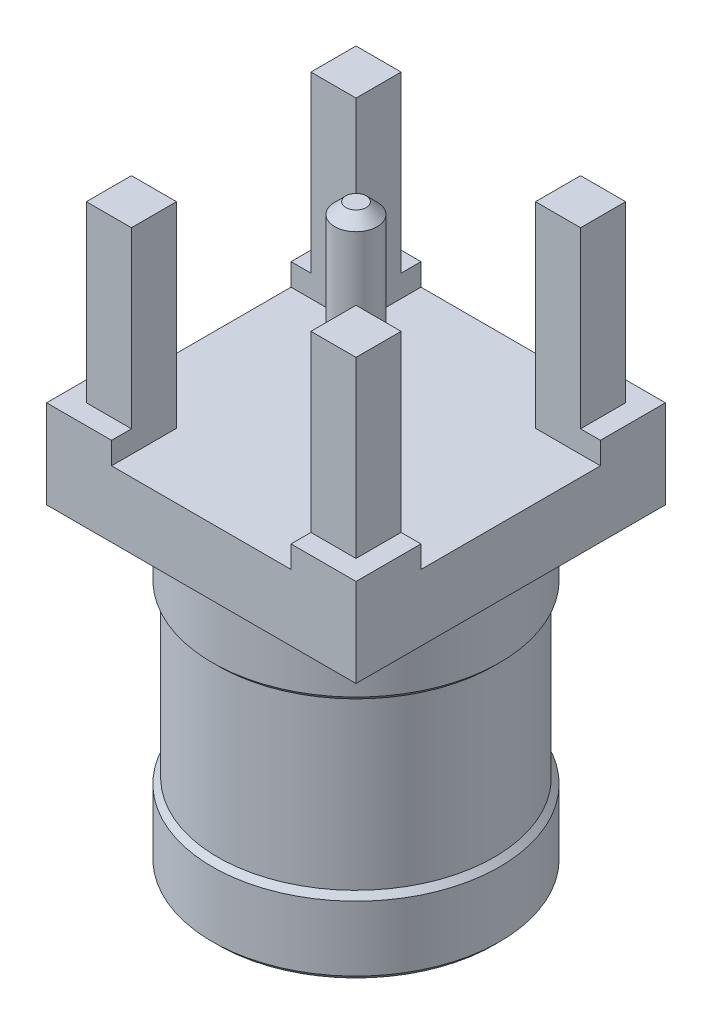
SolidWorks part; units mm, degrees
ref_plane "Front Plane" through (0, 0, 0) normal (0, 0, 1) x (1, 0, 0)
ref_plane "Top Plane" through (0, 0, 0) normal (0, 1, 0) x (1, 0, 0)
ref_plane "Right Plane" through (0, 0, 0) normal (1, 0, 0) x (0, 0, -1)
sketch "Sketch1" plane through (0, 0, 0) normal (0, 1, 0) x (1, 0, 0)
  line L1 (-3.5, -3.5) -> (3.5, -3.5)
  line L2 (-3.5, -3.5) -> (-3.5, 3.5)
  line L3 (-3.5, 3.5) -> (3.5, 3.5)
  line L4 (3.5, -3.5) -> (3.5, 3.5)
  line L5 (-3.5, -3.5) -> (3.5, 3.5) construction
  line L6 (-3.5, 3.5) -> (3.5, -3.5) construction
  point P0 (0, 0)
  dimension "D1" = 7
extrude "Boss-Extrude1" add sketch "Sketch1" along normal blind 1.5
sketch "Sketch2" plane through (0, 1.5, 0) normal (0, 1, 0) x (1, 0, 0)
  line L1 (-3.5, 3.5) -> (-2.03, 3.5)
  line L2 (-3.5, 3.5) -> (-3.5, 2.03)
  line L3 (-3.5, 2.03) -> (-2.03, 2.03)
  line L4 (-2.03, 3.5) -> (-2.03, 2.03)
  line L5 (3.5, 3.5) -> (2.03, 3.5)
  line L6 (3.5, 3.5) -> (3.5, 2.03)
  line L7 (3.5, 2.03) -> (2.03, 2.03)
  line L8 (2.03, 3.5) -> (2.03, 2.03)
  line L9 (3.5, -3.5) -> (2.03, -3.5)
  line L10 (3.5, -3.5) -> (3.5, -2.03)
  line L11 (3.5, -2.03) -> (2.03, -2.03)
  line L12 (2.03, -3.5) -> (2.03, -2.03)
  line L13 (-3.5, -3.5) -> (-2.03, -3.5)
  line L14 (-3.5, -3.5) -> (-3.5, -2.03)
  line L15 (-3.5, -2.03) -> (-2.03, -2.03)
  line L16 (-2.03, -3.5) -> (-2.03, -2.03)
  dimension "D1" = 1.47
extrude "Boss-Extrude2" add sketch "Sketch2" along normal blind 0.5
sketch "Sketch3" plane through (0, 2, 0) normal (0, 1, 0) x (1, 0, 0)
  line L1 (-2.03, -2.03) -> (-3.05, -2.03)
  line L2 (-2.03, -2.03) -> (-2.03, -3.05)
  line L3 (-2.03, -3.05) -> (-3.05, -3.05)
  line L4 (-3.05, -2.03) -> (-3.05, -3.05)
  line L5 (2.03, -2.03) -> (3.05, -2.03)
  line L6 (2.03, -2.03) -> (2.03, -3.05)
  line L7 (2.03, -3.05) -> (3.05, -3.05)
  line L8 (3.05, -2.03) -> (3.05, -3.05)
  line L9 (2.03, 2.03) -> (3.05, 2.03)
  line L10 (2.03, 2.03) -> (2.03, 3.05)
  line L11 (2.03, 3.05) -> (3.05, 3.05)
  line L12 (3.05, 2.03) -> (3.05, 3.05)
  line L13 (-2.03, 2.03) -> (-3.05, 2.03)
  line L14 (-2.03, 2.03) -> (-2.03, 3.05)
  line L15 (-2.03, 3.05) -> (-3.05, 3.05)
  line L16 (-3.05, 2.03) -> (-3.05, 3.05)
  dimension "D1" = 1.02
extrude "Boss-Extrude3" add sketch "Sketch3" along normal blind 3.94
sketch "Sketch4" plane through (0, 0, 0) normal (0, -1, 0) x (1, 0, 0)
  line L3 (0, -3.25) -> (1.4469, -3.25) construction
  line L4 (3.5, -3.5) -> (-3.5, -3.5) construction
  circle A0 centre (0, 0) radius 3.25
  circle A1 centre (0, 0) radius 1.6
  dimension "D1" = 0.25
  dimension "D2" = 3.2
extrude "Boss-Extrude4" add sketch "Sketch4" along normal offset from surface (7.06 mm away) 9.06 up to face at (2.86, 2, -2.86)
chamfer "Chamfer1" distance 0.125 angle 45 2 edges at (0, -7.06, -1.6) (0, -7.06, -3.25)
sketch "Sketch5" plane through (0, 0, 0) normal (0, 0, 1) x (1, 0, 0)
  line L0 (-3.25, -1.4675) -> (-3.125, -1.5925)
  line L1 (-3.25, 0) -> (-3.25, -6.935) construction
  line L2 (-3.125, -1.5925) -> (-3.125, -5.3425)
  line L3 (-3.125, -5.3425) -> (-3.25, -5.4675)
  line L4 (-3.25, -5.4675) -> (-3.25, -1.4675)
  line L6 (3.25, -3.4675) -> (-3.25, -3.4675) construction
  line L7 (3.25, -6.935) -> (3.25, 0) construction
  line L8 (-3.25, 0) -> (-3.125, 0)
  line L9 (3.5, 0) -> (-3.5, 0) construction
  line L10 (-3.125, 0) -> (-3.25, -0.125)
  line L11 (-3.25, -0.125) -> (-3.25, 0)
  dimension "D1" = 45
  dimension "D2" = 4
  dimension "D3" = 0.125
  dimension "D4" = 45
ref_axis "Axis1" through (0, -6.81, 0) along (0, 1, 0)
revolve "Cut-Revolve1" cut sketch "Sketch5" angle 360 about axis through (0, -6.81, 0) along (0, 1, 0)
sketch "Sketch7" plane through (0, 1.5, 0) normal (0, 1, 0) x (1, 0, 0)
  circle A0 centre (0, 0) radius 0.48
  dimension "D1" = 0.96
extrude "Boss-Extrude5" add sketch "Sketch7" along normal up to surface (4.44 mm away) up to face at (2.54, 5.94, -2.54)
chamfer "Chamfer2" distance 0.25 angle 45 1 edges at (0, 5.94, -0.48)
sketch "Sketch8" plane through (0, 5.94, 0) normal (0, 1, 0) x (1, 0, 0)
  line L0 (2.54, -2.03) -> (2.54, -3.05) construction
  line L1 (3.05, -2.03) -> (2.03, -2.03) construction
  line L2 (2.03, -3.05) -> (3.05, -3.05) construction
  line L3 (-2.03, 2.54) -> (-3.05, 2.54) construction
  line L4 (-2.03, 2.03) -> (-2.03, 3.05) construction
  line L5 (-3.05, 3.05) -> (-3.05, 2.03) construction
  point P12 (-2.54, 2.54)
  point P13 (2.54, -2.54)
ref_axis "Axis2" through (2.54, 5.94, 2.54) along (0, -1, 0)
ref_axis "Axis3" through (-2.54, 5.94, -2.54) along (0, -1, 0)
